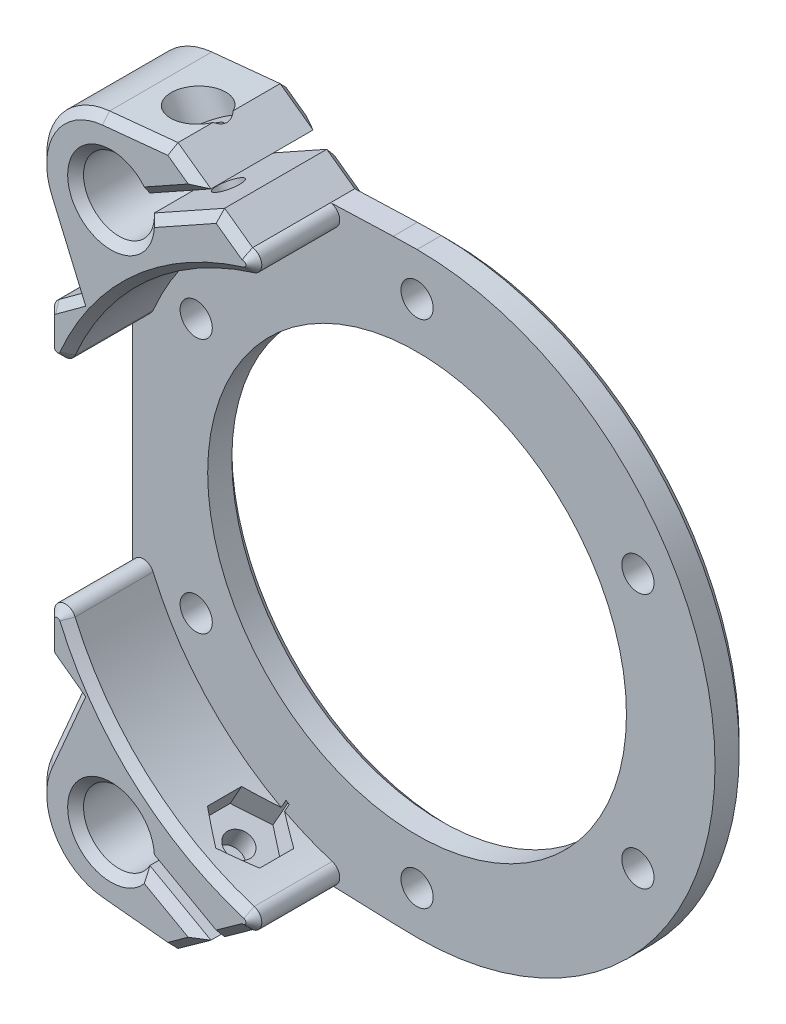
SolidWorks part; units mm, degrees
ref_plane "Front Plane" through (0, 0, 0) normal (0, 0, 1) x (1, 0, 0)
ref_plane "Top Plane" through (0, 0, 0) normal (0, 1, 0) x (1, 0, 0)
ref_plane "Right Plane" through (0, 0, 0) normal (1, 0, 0) x (0, 0, -1)
sketch "Sketch1" plane through (0, 0, 0) normal (0, 0, 1) x (1, 0, 0)
  line L0 (0, 36.75) -> (-10, 33.3337)
  line L1 (-10, 33.3337) -> (-15, 29)
  line L2 (-15, 29) -> (-58.05, 27.5)
  line L3 (-58.05, 27.5) -> (-76.5, 14)
  line L4 (-76.5, 14) -> (-76.5, -14)
  line L5 (-87.0431, 0) -> (20.0163, 0) construction
  line L6 (0, 32.2788) -> (0, 0) construction
  line L7 (76.5, 14) -> (76.5, -14)
  line L8 (58.05, 27.5) -> (76.5, 14)
  line L9 (15, 29) -> (58.05, 27.5)
  line L10 (10, 33.3337) -> (15, 29)
  line L11 (0, 36.75) -> (10, 33.3337)
  line L12 (0, -36.75) -> (10, -33.3337)
  line L13 (10, -33.3337) -> (15, -29)
  line L14 (15, -29) -> (58.05, -27.5)
  line L15 (58.05, -27.5) -> (76.5, -14)
  line L16 (-58.05, -27.5) -> (-76.5, -14)
  line L17 (-15, -29) -> (-58.05, -27.5)
  line L18 (-10, -33.3337) -> (-15, -29)
  line L19 (0, -36.75) -> (-10, -33.3337)
  circle A0 centre (0, 30) radius 3
  circle A1 centre (-50, 0) radius 19.5
  circle A2 centre (50, 0) radius 19.5
  circle A3 centre (0, -30) radius 3
  point P35 (76.5, 0)
  point P36 (-76.5, 0)
  dimension "D1" = 6
  dimension "D2" = 39
  dimension "D3" = 60
  dimension "D4" = 100
  dimension "D5" = 153
  dimension "D6" = 73.5
  dimension "D7" = 28
  dimension "D8" = 55
  dimension "D9" = 18.45
  dimension "D10" = 30
  dimension "D11" = 20
  dimension "D12" = 58
extrude "Boss-Extrude1" add sketch "Sketch1" along normal blind 3
sketch "Sketch2" plane through (0, 0, 3) normal (0, 0, 1) x (1, 0, 0)
  line L1 (8.5, 20) -> (-8.5, 20)
  line L2 (12.5, 16) -> (12.5, -16)
  line L3 (8.5, -20) -> (-8.5, -20)
  line L4 (-12.5, 16) -> (-12.5, -16)
  line L5 (12.5, 20) -> (-12.5, -20) construction
  line L6 (12.5, -20) -> (-12.5, 20) construction
  arc A1 (8.5, 20) -> (12.5, 16) centre (8.5, 16) cw
  arc A2 (12.5, -16) -> (8.5, -20) centre (8.5, -16) cw
  arc A3 (-8.5, -20) -> (-12.5, -16) centre (-8.5, -16) cw
  arc A4 (-8.5, 20) -> (-12.5, 16) centre (-8.5, 16) ccw
  point P0 (0, 0)
  dimension "D1" = 4
  dimension "D2" = 25
  dimension "D3" = 40
extrude "Cut-Extrude1" cut sketch "Sketch2" against normal through all
sketch "Sketch3" plane through (0, 0, 3) normal (0, 0, 1) x (1, 0, 0)
  line L0 (-58.05, 27.5) -> (-65, 32.5)
  line L1 (-58.05, 27.5) -> (-76.5, 14) construction
  line L2 (-65, 32.5) -> (-80.2046, 31)
  line L3 (-80.2046, 31) -> (-73.7667, 16)
  line L4 (-73.7667, 16) -> (-58.05, 27.5)
  line L5 (0, 0) -> (0, 46.5274) construction
  line L6 (73.7667, 16) -> (58.05, 27.5)
  line L7 (80.2046, 31) -> (73.7667, 16)
  line L8 (65, 32.5) -> (80.2046, 31)
  line L9 (58.05, 27.5) -> (65, 32.5)
  line L10 (0, 0) -> (-26.0239, 0) construction
  line L11 (58.05, -27.5) -> (65, -32.5)
  line L12 (65, -32.5) -> (80.2046, -31)
  line L13 (80.2046, -31) -> (73.7667, -16)
  line L14 (73.7667, -16) -> (58.05, -27.5)
  line L15 (-73.7667, -16) -> (-58.05, -27.5)
  line L16 (-80.2046, -31) -> (-73.7667, -16)
  line L17 (-65, -32.5) -> (-80.2046, -31)
  line L18 (-58.05, -27.5) -> (-65, -32.5)
  line L19 (-15, 29) -> (-58.05, 27.5) construction
  circle A0 centre (-70.5, 25.5) radius 3.3
  circle A1 centre (70.5, 25.5) radius 3.3
  circle A2 centre (-70.5, -25.5) radius 3.3
  circle A3 centre (70.5, -25.5) radius 3.3
  dimension "D1" = 6.6
  dimension "D2" = 70.5
  dimension "D3" = 25.5
  dimension "D4" = 62
  dimension "D5" = 65
  dimension "D6" = 32
  dimension "D7" = 80.2046
  dimension "D8" = 65
extrude "Boss-Extrude2" add sketch "Sketch3" against normal up to surface (3 mm away) up to face at (0, 0, 0)
fillet "Fillet1" radius 6.5 4 edges at (-80.2046, 31, 1.5) (-80.2046, -31, 1.5) (80.2046, -31, 1.5) (80.2046, 31, 1.5)
sketch "Sketch4" plane through (0, 0, 3) normal (0, 0, 1) x (1, 0, 0)
  line L0 (0, 48.5627) -> (0, -47.8194) construction
  circle A0 centre (-50, 0) radius 23.75 construction
  circle A1 centre (-50, 23.75) radius 1.5
  circle A2 centre (-70.5681, 11.875) radius 1.5
  circle A3 centre (-70.5681, -11.875) radius 1.5
  circle A4 centre (-50, -23.75) radius 1.5
  circle A5 centre (-29.4319, -11.875) radius 1.5
  circle A6 centre (-29.4319, 11.875) radius 1.5
  circle A7 centre (29.4319, 11.875) radius 1.5
  circle A8 centre (29.4319, -11.875) radius 1.5
  circle A9 centre (50, -23.75) radius 1.5
  circle A10 centre (70.5681, -11.875) radius 1.5
  circle A11 centre (70.5681, 11.875) radius 1.5
  circle A12 centre (50, 23.75) radius 1.5
  point P21 (-50, 0)
  point P31 (50, 0)
  dimension "D1" = 47.5
  dimension "D3" = 3
  dimension "D2" = 6
extrude "Cut-Extrude2" cut sketch "Sketch4" against normal through all
sketch "Sketch5" plane through (0, 0, 3) normal (0, 0, 1) x (1, 0, 0)
  line L12 (-57.9916, 27.5812) -> (-50, 27.75)
  line L13 (-76.5591, 14.0807) -> (-76.5, 0)
  line L14 (-76.5, 14) -> (-76.5, -14) construction
  line L15 (-84.5459, 0) -> (89.0041, 0) construction
  line L16 (-73.89, 16.0337) -> (-76.5591, 14.0807)
  line L17 (-76.7941, 22.8002) -> (-73.89, 16.0337)
  line L18 (-64.9722, 32.6032) -> (-71.3771, 31.9714)
  line L19 (-57.9916, 27.5812) -> (-64.9722, 32.6032)
  line L20 (-73.89, 16.0337) -> (-76.5591, 14.0807)
  line L21 (-76.7941, 22.8002) -> (-73.89, 16.0337)
  line L22 (-64.9722, 32.6032) -> (-71.3771, 31.9714)
  line L23 (-57.9916, 27.5812) -> (-64.9722, 32.6032)
  line L24 (-57.9916, -27.5812) -> (-64.9722, -32.6032)
  line L25 (-64.9722, -32.6032) -> (-71.3771, -31.9714)
  line L26 (-76.7941, -22.8002) -> (-73.89, -16.0337)
  line L27 (-73.89, -16.0337) -> (-76.5591, -14.0807)
  line L28 (-76.5591, -14.0807) -> (-76.5, 0)
  line L29 (-57.9916, -27.5812) -> (-50, -27.75)
  line L31 (-98.6251, 56.8967) -> (99.3355, 56.8967)
  line L32 (-98.6251, 56.8967) -> (-98.6251, -48.9335)
  line L33 (-98.6251, -48.9335) -> (99.3355, -48.9335)
  line L34 (99.3355, 56.8967) -> (99.3355, -48.9335)
  arc A0 (-50, -27.75) -> (-50, 27.75) centre (-50, 0) ccw
  arc A4 (-71.3771, -31.9714) -> (-76.7941, -22.8002) centre (-70.7291, -25.4032) cw
  arc A5 (-71.3771, 31.9714) -> (-76.7941, 22.8002) centre (-70.7291, 25.4032) ccw
  arc A6 (-71.3771, 31.9714) -> (-76.7941, 22.8002) centre (-70.7291, 25.4032) ccw
  dimension "D1" = 55.5
  dimension "D2" = 0.1
extrude "Cut-Extrude3" cut sketch "Sketch5" against normal through all
sketch "Sketch6" plane through (0, 0, 3) normal (0, 0, 1) x (1, 0, 0)
  line L0 (-76.7022, 22.8396) -> (-73.7667, 16)
  line L1 (-76.7022, 22.8396) -> (-73.7667, 16) construction
  line L2 (-71.3673, 31.8718) -> (-65, 32.5)
  line L3 (-65, 32.5) -> (-58.05, 27.5)
  line L4 (-58.05, 27.5) -> (-50, 26.75)
  line L5 (-76.5, 14) -> (-73.7667, 16)
  line L6 (-76.5, 14) -> (-76.5, 3.6486)
  line L7 (-76.5, 14) -> (-76.5, -14) construction
  line L8 (-50, 0) -> (-84.0522, 0) construction
  line L9 (-76.5, -14) -> (-76.5, -3.6486)
  line L10 (-76.5, -14) -> (-73.7667, -16)
  line L11 (-58.05, -27.5) -> (-50, -26.75)
  line L12 (-65, -32.5) -> (-58.05, -27.5)
  line L13 (-71.3673, -31.8718) -> (-65, -32.5)
  line L14 (-76.7022, -22.8396) -> (-73.7667, -16)
  arc A0 (-50, 26.75) -> (-76.5, 3.6486) centre (-50, 0) ccw
  arc A1 (-76.7022, 22.8396) -> (-71.3673, 31.8718) centre (-70.7291, 25.4032) cw
  arc A2 (-76.7022, -22.8396) -> (-71.3673, -31.8718) centre (-70.7291, -25.4032) ccw
  arc A3 (-50, -26.75) -> (-76.5, -3.6486) centre (-50, 0) cw
  circle A4 centre (-70.5, 25.5) radius 3.3
  circle A5 centre (-70.5, 25.5) radius 3.3 construction
  circle A6 centre (-70.5, -25.5) radius 3.3
  dimension "D1" = 53.5
extrude "Boss-Extrude3" add sketch "Sketch6" along normal blind 8
fillet "Fillet2" radius 1 6 edges at (-50, -26.75, 7) (-76.5, -3.6486, 7) (-50, 26.75, 7) (-76.5, 3.6486, 7) (-76.5, -14, 5.5) (-76.5, 14, 5.5)
sketch "Sketch7" plane through (0, 0, 11) normal (0, 0, 1) x (1, 0, 0)
  line L0 (-68.7299, 26.5013) -> (-57.4519, 32.7968)
  line L1 (-57.4519, 32.7968) -> (-56.7571, 31.5522)
  line L2 (-56.7571, 31.5522) -> (-67.9885, 25.2827)
  line L3 (-67.9885, 25.2827) -> (-68.7299, 26.5013)
  line L4 (-70.5, 25.5) -> (-59.611, 31.5783) construction
  line L5 (-50, 0) -> (-95.3725, 0) construction
  line L6 (-70.5, -25.5) -> (-59.611, -31.5783) construction
  line L7 (-67.9885, -25.2827) -> (-68.7299, -26.5013)
  line L8 (-56.7571, -31.5522) -> (-67.9885, -25.2827)
  line L9 (-57.4519, -32.7968) -> (-56.7571, -31.5522)
  line L10 (-68.7299, -26.5013) -> (-57.4519, -32.7968)
extrude "Cut-Extrude4" cut sketch "Sketch7" against normal through all
sketch "Sketch8" plane through (-26.9121, 48.2118, 0) normal (-0.4874, 0.8732, 0) x (0.8732, 0.4874, 0)
  circle A0 centre (-43.0415, -6.0725) radius 1.2
  dimension "D1" = 2.4
extrude "Cut-Extrude5" cut sketch "Sketch8" against normal blind 18 from offset 10
sketch "Sketch9" plane through (-26.9121, 48.2118, 0) normal (-0.4874, 0.8732, 0) x (0.8732, 0.4874, 0)
  circle A0 centre (-43.0415, -6.0725) radius 2.325
  dimension "D1" = 4.65
extrude "Cut-Extrude6" cut sketch "Sketch9" against normal blind 6 from offset 10
sketch "Sketch10" plane through (-26.9121, 48.2118, 0) normal (-0.4874, 0.8732, 0) x (0.8732, 0.4874, 0)
  line L1 (-43.0415, -2.8971) -> (-45.7915, -4.4848)
  line L2 (-45.7915, -4.4848) -> (-45.7915, -7.6602)
  line L3 (-45.7915, -7.6602) -> (-43.0415, -9.2479)
  line L4 (-43.0415, -9.2479) -> (-40.2915, -7.6602)
  line L5 (-40.2915, -7.6602) -> (-40.2915, -4.4848)
  line L6 (-40.2915, -4.4848) -> (-43.0415, -2.8971)
  circle A0 centre (-43.0415, -6.0725) radius 2.75 construction
  dimension "D1" = 5.5
extrude "Cut-Extrude7" cut sketch "Sketch10" along normal blind 3 from offset 5 offset against normal yes
mirror "Mirror1" about plane through (0, 0, 0) normal (0, 1, 0) of "Cut-Extrude7", "Cut-Extrude6", "Cut-Extrude5"
chamfer "Chamfer1" distance 0.75 angle 45 33 edges at (-27.9319, 11.875, 0) (-27.9319, -11.875, 0) (-48.5, -23.75, 0) (-69.0681, -11.875, 0) (-69.0681, 11.875, 0) (-48.5, 23.75, 0) (-30.5, 0, 0) (-63.4672, 31.3973, 0) (-68.1836, 32.1859, 0) (-76.3257, 28.7089, 0) (-75.2344, 19.4198, 0) (-74.9286, 15.1498, 0) (-76.3918, 13.9451, 0) (-76.5, 0, 0) (-76.3918, -13.9451, 0) (-74.9286, -15.1498, 0) (-75.2344, -19.4198, 0) (-76.3257, -28.7089, 0) (-68.1836, -32.1859, 0) (-63.4672, -31.3973, 0) (-64.7793, -28.7066, 0) (-73.6627, -24.558, 0) (-63.932, -27.5471, 0) (-59.3534, -28.4377, 0) (-55.1362, -27.6015, 0) (-51.1112, -27.7265, 0) (-22.25, 0, 0) (-51.1112, 27.7265, 0) (-55.1362, 27.6015, 0) (-59.3534, 28.4377, 0) (-63.932, 27.5471, 0) (-73.6627, 24.558, 0) (-64.7793, 28.7066, 0)
chamfer "Chamfer2" distance 0.74 angle 45 28 edges at (-63.4672, -31.3973, 11) (-64.7793, -28.7066, 11) (-59.3534, -28.4377, 11) (-63.932, -27.5471, 11) (-73.6627, -24.558, 11) (-68.1836, -32.1859, 11) (-57.2017, -26.5863, 11) (-76.3257, -28.7089, 11) (-75.2344, -19.4198, 11) (-74.9286, -15.1498, 11) (-76.3918, -13.9451, 11) (-76.5, -12.2192, 11) (-75.7013, -9.9664, 11) (-67.8912, -19.8864, 11) (-74.9286, 15.1498, 11) (-76.3918, 13.9451, 11) (-75.2344, 19.4198, 11) (-76.5, 12.2192, 11) (-76.3257, 28.7089, 11) (-75.7013, 9.9664, 11) (-68.1836, 32.1859, 11) (-63.4672, 31.3973, 11) (-64.7793, 28.7066, 11) (-73.6627, 24.558, 11) (-63.932, 27.5471, 11) (-59.3534, 28.4377, 11) (-57.2017, 26.5863, 11) (-67.8912, 19.8864, 11)
